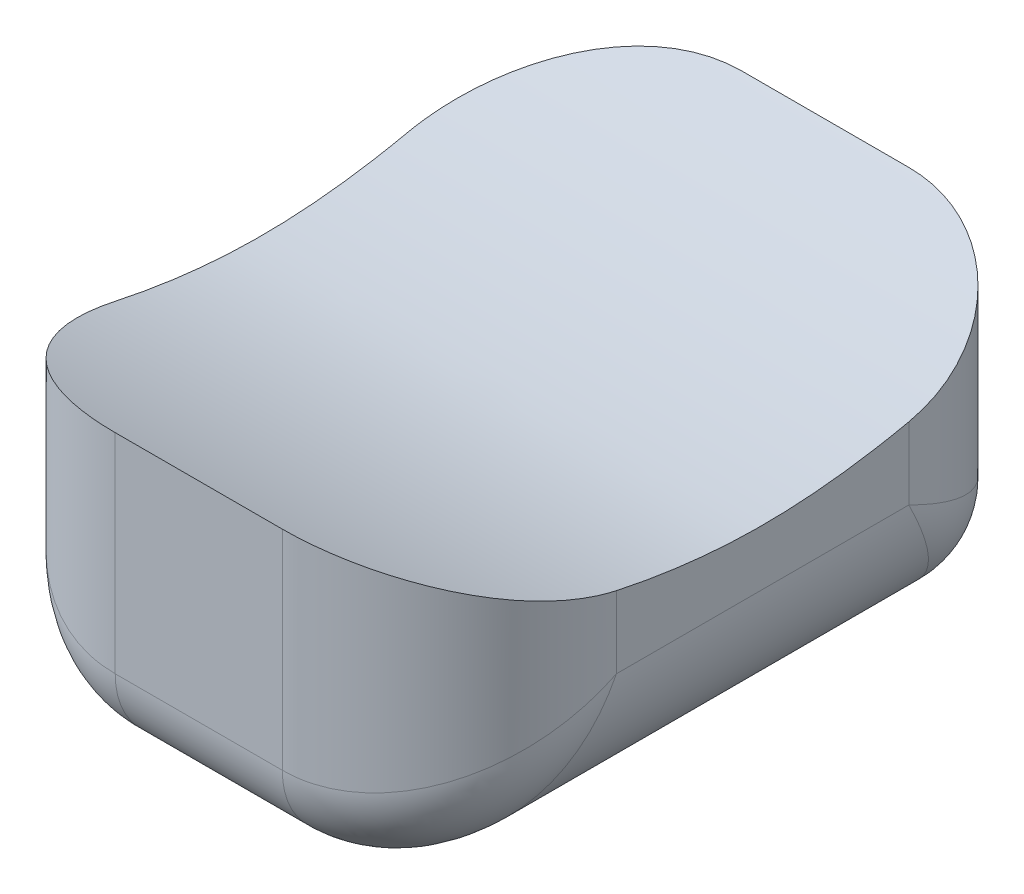
SolidWorks part; units mm, degrees
ref_plane "Front Plane" through (0, 0, 0) normal (0, 0, 1) x (1, 0, 0)
ref_plane "Top Plane" through (0, 0, 0) normal (0, 1, 0) x (1, 0, 0)
ref_plane "Right Plane" through (0, 0, 0) normal (1, 0, 0) x (0, 0, -1)
sketch "Sketch1" plane through (0, 0, 0) normal (1, 0, 0) x (0, 0, -1)
  line L1 (-2.75, -1.75) -> (2.75, -1.75)
  line L2 (-3.75, -0.75) -> (-3.75, 1.75)
  line L4 (3.75, -0.75) -> (3.75, 1.75)
  line L5 (-3.75, -1.75) -> (3.75, 1.75) construction
  line L6 (-3.75, 1.75) -> (3.75, -1.75) construction
  arc A0 (-2.75, -1.75) -> (-3.75, -0.75) centre (-2.75, -0.75) cw
  arc A1 (2.75, -1.75) -> (3.75, -0.75) centre (2.75, -0.75) ccw
  spline S0 degree 3 poles (-3.75, 1.75) (-2.5714, 1.2598) (0, 0.5718) (2.5714, 1.2598) (3.75, 1.75) knots 0 0 0 0 0.5 1 1 1 1
  point P0 (0, 0)
  dimension "D3" = 1
  dimension "D1" = 3.5
  dimension "D2" = 7.5
extrude "Boss-Extrude2" add sketch "Sketch1" along normal blind 6 contours S0 L4 A1 L1 A0 L2
fillet "Fillet2" radius 2 5 edges at (6, 0.5, 3.75) (6, -1.4571, 3.4571) (6, 0.5, -3.75) (6, -1.4571, -3.4571) (6, -1.75, 0)
fillet "Fillet5" radius 2 5 edges at (0, 0.5, 3.75) (0, -1.4571, 3.4571) (0, 0.5, -3.75) (0, -1.4571, -3.4571) (0, -1.75, 0)
